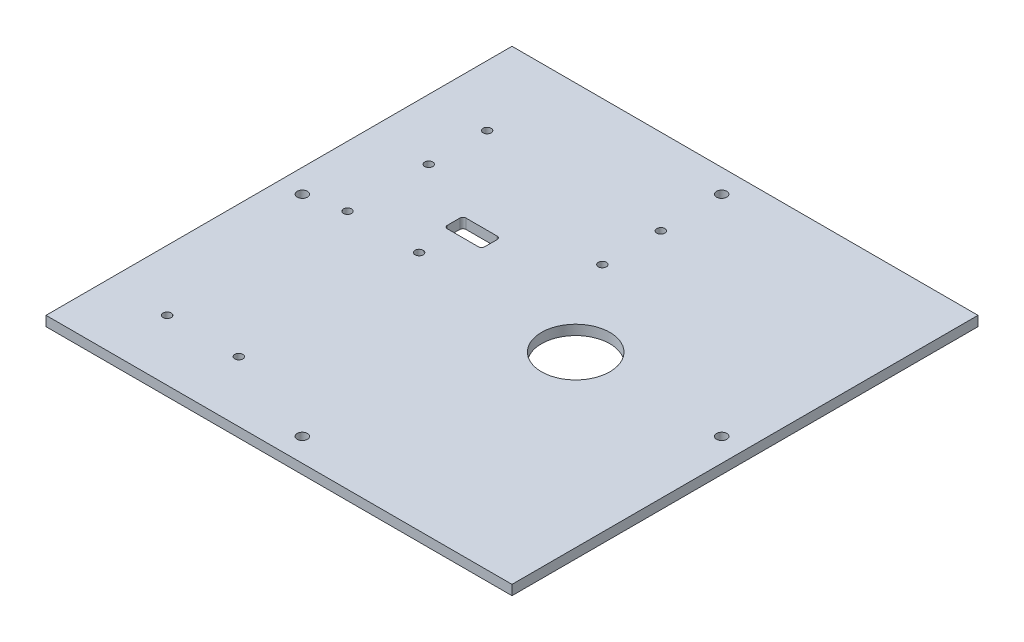
SolidWorks part; units mm, degrees
ref_plane "Front Plane" through (0, 0, 0) normal (0, 0, 1) x (1, 0, 0)
ref_plane "Top Plane" through (0, 0, 0) normal (0, 1, 0) x (1, 0, 0)
ref_plane "Right Plane" through (0, 0, 0) normal (1, 0, 0) x (0, 0, -1)
sketch "Sketch1" plane through (0, 0, 0) normal (0, 1, 0) x (1, 0, 0)
  line L1 (-70.5343, 75) -> (79.4657, 75)
  line L2 (-70.5343, 75) -> (-70.5343, -75)
  line L3 (-70.5343, -75) -> (79.4657, -75)
  line L4 (79.4657, 75) -> (79.4657, -75)
  line L5 (-70.5343, 75) -> (79.4657, -75) construction
  line L6 (-70.5343, -75) -> (79.4657, 75) construction
  line L7 (-63.0343, 67.5) -> (71.9657, 67.5) construction
  line L8 (-63.0343, 67.5) -> (-63.0343, -67.5) construction
  line L9 (-63.0343, -67.5) -> (71.9657, -67.5) construction
  line L10 (71.9657, 67.5) -> (71.9657, -67.5) construction
  line L11 (-63.0343, 67.5) -> (71.9657, -67.5) construction
  line L12 (-63.0343, -67.5) -> (71.9657, 67.5) construction
  line L13 (-51.0343, -55.5) -> (-27.9843, -55.5) construction
  line L14 (-51.0343, -55.5) -> (-51.0343, 2.55) construction
  line L15 (-51.0343, 2.55) -> (-27.9843, 2.55) construction
  line L16 (-27.9843, -55.5) -> (-27.9843, 2.55) construction
  line L17 (-51.0343, 47.5) -> (4.8657, 47.5) construction
  line L18 (-51.0343, 47.5) -> (-51.0343, 28.7) construction
  line L19 (-51.0343, 28.7) -> (4.8657, 28.7) construction
  line L20 (4.8657, 47.5) -> (4.8657, 28.7) construction
  line L25 (-30.0343, 19.7) -> (-20.0343, 19.7)
  line L26 (-31.0343, 18.7) -> (-31.0343, 14.7)
  line L27 (-30.0343, 13.7) -> (-20.0343, 13.7)
  line L28 (-19.0343, 18.7) -> (-19.0343, 14.7)
  circle A0 centre (-63.0343, 0) radius 1.65
  circle A1 centre (4.4657, 67.5) radius 1.65
  circle A2 centre (71.9657, 0) radius 1.65
  circle A3 centre (4.4657, -67.5) radius 1.65
  circle A5 centre (-51.0343, -55.5) radius 1.3
  circle A6 centre (-27.9843, -55.5) radius 1.3
  circle A7 centre (-27.9843, 2.55) radius 1.3
  circle A8 centre (-51.0343, 2.55) radius 1.3
  circle A9 centre (4.8657, 47.5) radius 1.3
  circle A10 centre (4.8657, 28.7) radius 1.3
  circle A11 centre (-51.0343, 47.5) radius 1.3
  circle A12 centre (-51.0343, 28.7) radius 1.3
  circle A13 centre (24.9657, 0) radius 11
  arc A18 (-31.0343, 14.7) -> (-30.0343, 13.7) centre (-30.0343, 14.7) ccw
  arc A19 (-20.0343, 13.7) -> (-19.0343, 14.7) centre (-20.0343, 14.7) ccw
  arc A20 (-20.0343, 19.7) -> (-19.0343, 18.7) centre (-20.0343, 18.7) cw
  arc A21 (-30.0343, 19.7) -> (-31.0343, 18.7) centre (-30.0343, 18.7) ccw
  point P0 (4.4657, 0)
  point P6 (4.4657, 0)
  point P42 (-31.0343, 13.7)
  point P47 (-19.0343, 19.7)
  point P50 (-31.0343, 19.7)
  dimension "D5" = 3.3
  dimension "D6" = 22
  dimension "D9" = 2.6
  dimension "D13" = 2.6
  dimension "D17" = 47
  dimension "D18" = 6
  dimension "D20" = 1
  dimension "D1" = 7.5
  dimension "D2" = 7.5
  dimension "D3" = 150
  dimension "D4" = 150
  dimension "D7" = 58.05
  dimension "D8" = 23.05
  dimension "D10" = 12
  dimension "D11" = 12
  dimension "D12" = 55.9
  dimension "D14" = 18.8
  dimension "D15" = 20
  dimension "D16" = 12
  dimension "D19" = 12
  dimension "D21" = 32
  dimension "D22" = 9
extrude "Boss-Extrude1" add sketch "Sketch1" along normal blind 3.175
